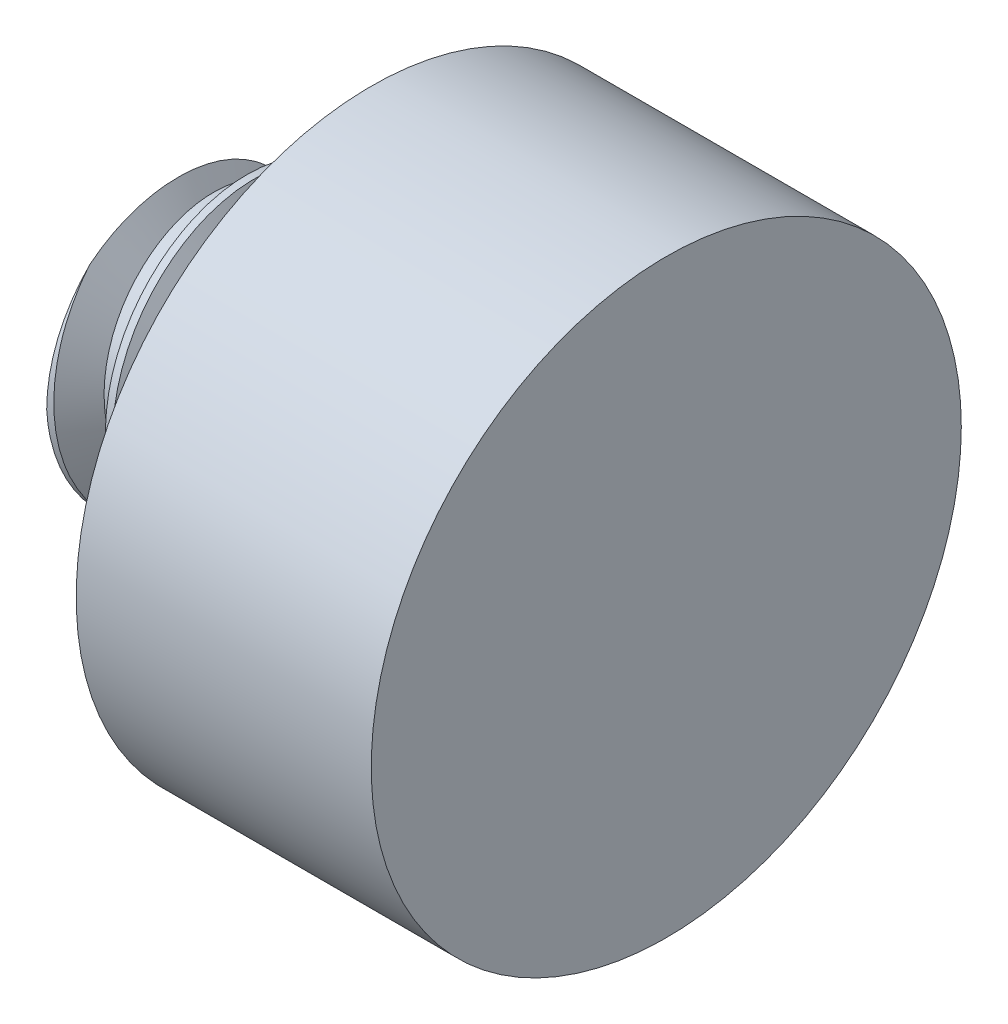
SolidWorks part; units mm, degrees
ref_plane "Front Plane" through (0, 0, 0) normal (0, 0, 1) x (1, 0, 0)
ref_plane "Top Plane" through (0, 0, 0) normal (0, 1, 0) x (1, 0, 0)
ref_plane "Right Plane" through (0, 0, 0) normal (1, 0, 0) x (0, 0, -1)
sketch "Sketch1" plane through (0, 0, 0) normal (0, 0, 1) x (1, 0, 0)
  line L0 (0, 0) -> (0, 3.175)
  line L1 (0, 3.175) -> (3.81, 3.175)
  line L2 (3.81, 3.175) -> (3.81, 6.35)
  line L3 (3.81, 6.35) -> (10.16, 6.35)
  line L4 (10.16, 6.35) -> (10.16, 0)
  line L5 (55, 0) -> (-55, 0) construction
  line L6 (10.16, 0) -> (0, 0)
  dimension "D1" = 3.175
  dimension "D2" = 6.35
  dimension "D3" = 6.35
  dimension "D4" = 3.81
revolve "Revolve1" add sketch "Sketch1" angle 360 about L6
thread "Thread1" pitch 1.27 method cut profile "Thread Profile1" start angle 0, offset 0, length 3.81, pitch 1.27, diameter 6.35
ref_plane "Plane1" through (3.81, 0, 3.175) normal (0, -1, 0) x (0, 0, 1)
sketch "Thread Profile1" plane through (3.81, 0, 3.175) normal (0, -1, 0) x (0, 0, 1)
  line L0 (0, 0) -> (0, 1.27) construction
  line L11 (0, 0) -> (0, 1.1112)
  line L12 (0, 1.1112) -> (-0.6874, 0.7144)
  line L13 (-0.6874, 0.7144) -> (-0.6874, 0.3969)
  line L15 (-0.6874, 0.3969) -> (0, 0)
  line L17 (-0.6874, 0.5556) -> (0, 0.5556) construction
  point P2 (0, 0)
  dimension "Pitch" = 1.27
  dimension "Profile_Angle" = 60
  dimension "Profile_Land" = 0.3175
  dimension "Profile_Height" = 0.6874
